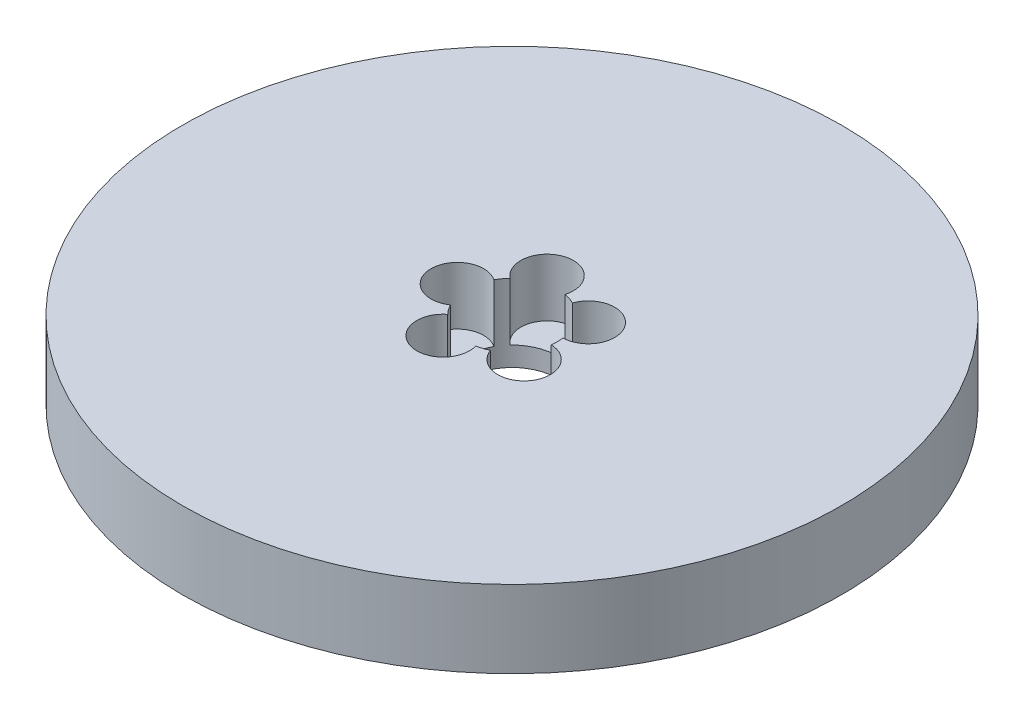
SolidWorks part; units mm, degrees
ref_plane "Front Plane" through (0, 0, 0) normal (0, 0, 1) x (1, 0, 0)
ref_plane "Top Plane" through (0, 0, 0) normal (0, 1, 0) x (1, 0, 0)
ref_plane "Right Plane" through (0, 0, 0) normal (1, 0, 0) x (0, 0, -1)
sketch "Sketch1" plane through (0, 0, 0) normal (0, 1, 0) x (1, 0, 0)
  circle A0 centre (0, 0) radius 72.5
  dimension "FLANGE_OD" = 145
extrude "Boss-Extrude1" add sketch "Sketch1" along normal blind 17
sketch "Sketch2" plane through (0, 0, 0) normal (0, 1, 0) x (1, 0, 0)
  circle A0 centre (0, 0) radius 10
  dimension "BORE_D" = 20
extrude "Cut-Extrude1" cut sketch "Sketch2" along normal through all
sketch "Sketch3" plane through (0, 17, 0) normal (0, 1, 0) x (1, 0, 0)
  circle A0 centre (0, 0) radius 12.0244 construction
  circle A1 centre (-12.0244, 0) radius 5.7874
  dimension "BOLT_D" = 11.5748
  dimension "BOLT_PCD" = 24.0488
extrude "Cut-Extrude2" cut sketch "Sketch3" against normal blind 12.7134
pattern_circular "CirPattern1" count 5 over 360 about axis through (0, 0, 0) along (0, 1, 0) of "Cut-Extrude2"
